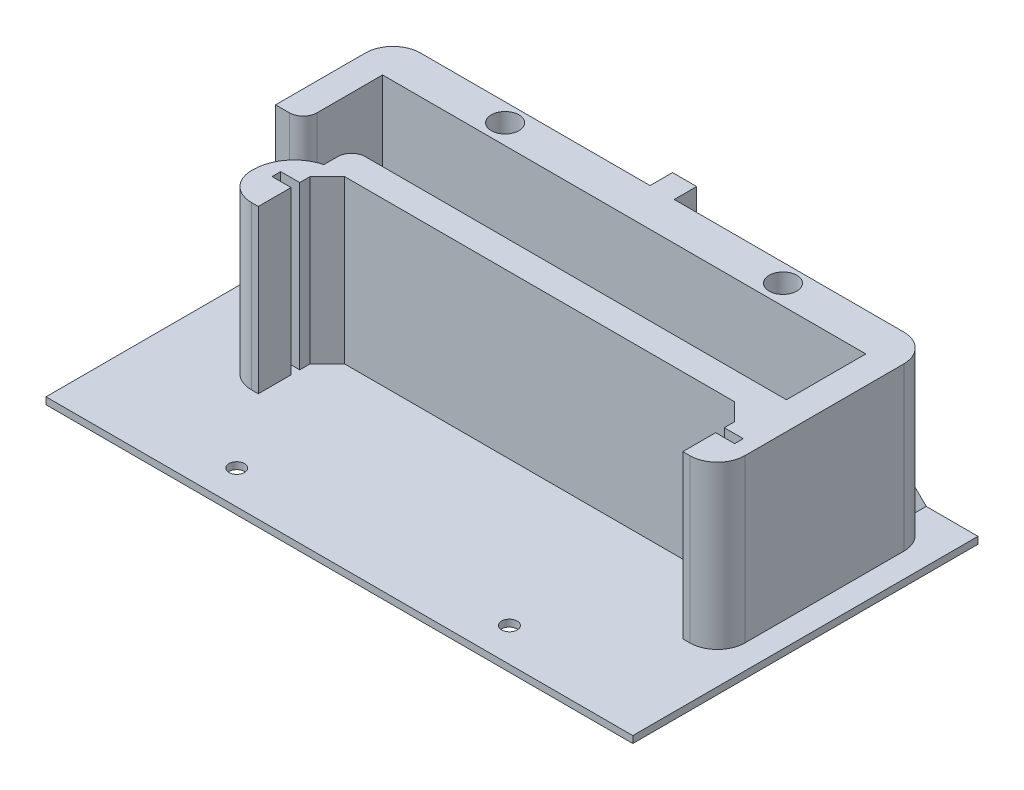
SolidWorks part; units mm, degrees
ref_plane "Front Plane" through (0, 0, 0) normal (0, 0, 1) x (1, 0, 0)
ref_plane "Top Plane" through (0, 0, 0) normal (0, 1, 0) x (1, 0, 0)
ref_plane "Right Plane" through (0, 0, 0) normal (1, 0, 0) x (0, 0, -1)
sketch "Sketch1" plane through (0, 0, 0) normal (0, 1, 0) x (1, 0, 0)
  line L1 (-85, -50) -> (85, -50)
  line L2 (-85, -50) -> (-85, 50)
  line L3 (-85, 50) -> (85, 50)
  line L4 (85, -50) -> (85, 50)
  line L5 (-85, -50) -> (85, 50) construction
  line L6 (-85, 50) -> (85, -50) construction
  point P0 (0, 0)
  dimension "D1" = 170
  dimension "D2" = 100
extrude "Boss-Extrude1" add sketch "Sketch1" along normal blind 2
sketch "Sketch14" plane through (0, 2, 0) normal (0, 1, 0) x (1, 0, 0)
  line L0 (-995.812, 38.25) -> (49004.188, 38.25) construction
  line L1 (-40.25, -963.5298) -> (-40.25, 49036.4702) construction
  line L2 (0, -1000) -> (0, 49000) construction
  line L3 (40.25, -963.5298) -> (40.25, 49036.4702) construction
  line L4 (-39.5, -988.4676) -> (-39.5, 49011.5324) construction
  line L5 (-1000, 0) -> (49000, 0) construction
  line L6 (-1000, -40.25) -> (49000, -40.25) construction
  line L7 (85, 50) -> (-85, 50) construction
  line L8 (-85, -50) -> (85, -50) construction
  line L9 (39.5, -993.7096) -> (39.5, 49006.2904) construction
  circle A0 centre (-40.25, 38.25) radius 2.25
  circle A1 centre (40.25, 38.25) radius 2.25
  circle A4 centre (-39.5, -40.25) radius 2.25
  circle A5 centre (39.5, -40.25) radius 2.25
  dimension "D6" = 39.5
  dimension "D8" = 0
  dimension "D10" = 4.5
  dimension "D12" = 4.5
  dimension "D7" = 4.5
  dimension "D13" = 4.5
  dimension "D1" = 40.25
  dimension "D2" = 40.25
  dimension "D3" = 11.75
  dimension "D4" = 9.75
  dimension "D5" = 39.5
  dimension "D9" = 0
  dimension "D11" = 0
extrude "Cut-Extrude7" cut sketch "Sketch14" against normal through all both and the other way through all
sketch "Sketch15" plane through (0, 2, 0) normal (0, 1, 0) x (1, 0, 0)
  line L0 (0, -1000) -> (0, 49000) construction
  line L1 (-1012.7555, 43.5) -> (48987.2445, 43.5) construction
  line L2 (85, 50) -> (-85, 50) construction
  line L4 (-3.5, 43.5) -> (-57.5, 43.5)
  line L5 (-3.5, 43.5) -> (-3.5, 50)
  line L6 (-3.5, 50) -> (-57.5, 50)
  line L7 (-57.5, 43.5) -> (-57.5, 50)
  line L8 (3.5, 43.5) -> (57.5, 43.5)
  line L9 (3.5, 43.5) -> (3.5, 50)
  line L10 (3.5, 50) -> (57.5, 50)
  line L11 (57.5, 43.5) -> (57.5, 50)
  dimension "D1" = 6.5
  dimension "D2" = 54
  dimension "D3" = 54
  dimension "D4" = 3.5
  dimension "D5" = 3.5
extrude "Cut-Extrude8" cut sketch "Sketch15" against normal through all both and the other way through all
sketch "Sketch16" plane through (0, 2, 0) normal (0, 1, 0) x (1, 0, 0)
  line L0 (-85, 50) -> (-85, -50) construction
  line L1 (-70, 43.5) -> (70, 43.5)
  line L2 (-70, 43.5) -> (-70, 32.5)
  line L3 (-70, 32.5) -> (70, 32.5)
  line L4 (70, 43.5) -> (70, 32.5)
  line L5 (-3.5, 43.5) -> (-57.5, 43.5) construction
  line L7 (-3.5, 50) -> (3.5, 50)
  line L8 (-3.5, 50) -> (-3.5, 43.5)
  line L9 (-3.5, 43.5) -> (3.5, 43.5)
  line L10 (3.5, 50) -> (3.5, 43.5)
  line L11 (-70, 43.5) -> (-78, 43.5)
  line L12 (-70, 43.5) -> (-70, 9.5)
  line L13 (-70, 9.5) -> (-78, 9.5)
  line L14 (-78, 43.5) -> (-78, 9.5)
  line L15 (70, 43.5) -> (78, 43.5)
  line L16 (70, 43.5) -> (70, 9.5)
  line L17 (70, 9.5) -> (78, 9.5)
  line L18 (78, 43.5) -> (78, 9.5)
  line L19 (78, 9.5) -> (-56, 9.5)
  line L20 (78, 9.5) -> (78, 1.5)
  line L21 (78, 1.5) -> (-56, 1.5)
  line L22 (-56, 9.5) -> (-56, 1.5)
  line L23 (78, 1.5) -> (68, 1.5)
  line L24 (78, 1.5) -> (78, -18.5)
  line L25 (78, -18.5) -> (68, -18.5)
  line L26 (68, 1.5) -> (68, -18.5)
  line L27 (-55, 1.5) -> (-65, 1.5)
  line L28 (-55, 1.5) -> (-55, -18.5)
  line L29 (-55, -18.5) -> (-65, -18.5)
  line L30 (-65, 1.5) -> (-65, -18.5)
  line L31 (-60.5, -6.5) -> (73.5, -6.5)
  line L32 (-60.5, -6.5) -> (-60.5, -9)
  line L33 (-60.5, -9) -> (73.5, -9)
  line L34 (73.5, -6.5) -> (73.5, -9)
  circle A0 centre (-40.25, 38.25) radius 4
  circle A1 centre (40.25, 38.25) radius 4
  point P36 (-55, -8.5)
  line M6 (3.5, 50) -> (-3.5, 50)
  line M7 (-3.5, 50) -> (-3.5, 43.5)
  line M8 (-3.5, 43.5) -> (-57.5, 43.5)
  line M16 (57.5, 43.5) -> (3.5, 43.5)
  line M17 (3.5, 43.5) -> (3.5, 50)
  dimension "D11" = 8
  dimension "D12" = 8
  dimension "D1" = 140
  dimension "D2" = 15
  dimension "D3" = 0
  dimension "D4" = 11
  dimension "D5" = 8
  dimension "D6" = 8
  dimension "D7" = 34
  dimension "D8" = 34
  dimension "D9" = 8
  dimension "D10" = 134
  dimension "D13" = 20
  dimension "D14" = 20
  dimension "D15" = 10
  dimension "D16" = 10
  dimension "D17" = 123
  dimension "D18" = 2.5
  dimension "D19" = 134
  dimension "D20" = 8
  dimension "D21" = 5.5
extrude "Boss-Extrude4" add sketch "Sketch16" along normal blind 47 contours L11 L14 L13 L12 L2 | L4 L1 L2 L3 A1 A0 M16 M8 | L1 M7 M17 M6 | L18 L15 L4 L16 L17 | L19 L22 L21 L20 L17 | L31 L34 L33 L26 L25 L24 L21 | L33 L32 L31 L28 L21 L27 L30 L29 region at (0, 2, -37.9825) region at (-74, 2, -26.5) region at (0, 2, -46.75) region at (74, 2, -26.5) region at (11, 2, -5.5) region at (77.7764, 2, 8.5) region at (-55.5, 2, -1.2764)
fillet "Fillet1" radius 4 2 edges at (-56, 25.5, -9.5) (-70, 25.5, -9.5)
chamfer "Chamfer1" distance 5 angle 45 2 edges at (68, 25.5, -1.5) (-55, 25.5, -1.5)
fillet "Fillet2" radius 8 4 edges at (-65, 25.5, 18.5) (78, 25.5, 18.5) (78, 25.5, -43.5) (-78, 25.5, -43.5)
sketch "Sketch17" plane through (0, 2, 0) normal (0, 1, 0) x (1, 0, 0)
  line L0 (-3.5, 43.5) -> (-70, 43.5) construction
  line L1 (-57.5, 50) -> (-70, 50)
  line L2 (-57.5, 50) -> (-57.5, 43.5)
  line L3 (-57.5, 43.5) -> (-70, 43.5)
  line L4 (-70, 50) -> (-70, 43.5)
  line L5 (-57.5, 43.5) -> (-70, 43.5) construction
  line L7 (57.5, 50) -> (70, 50)
  line L8 (57.5, 50) -> (57.5, 43.5)
  line L9 (57.5, 43.5) -> (70, 43.5)
  line L10 (70, 50) -> (70, 43.5)
  dimension "D1" = 12.5
extrude "Boss-Extrude5" add sketch "Sketch17" along normal blind 4
chamfer "Chamfer2" distance 4 angle 45 2 edges at (70, 6, -46.75) (-70, 6, -46.75)
fillet "Fillet3" radius 12 1 edges at (-65, 25.5, -1.5)
